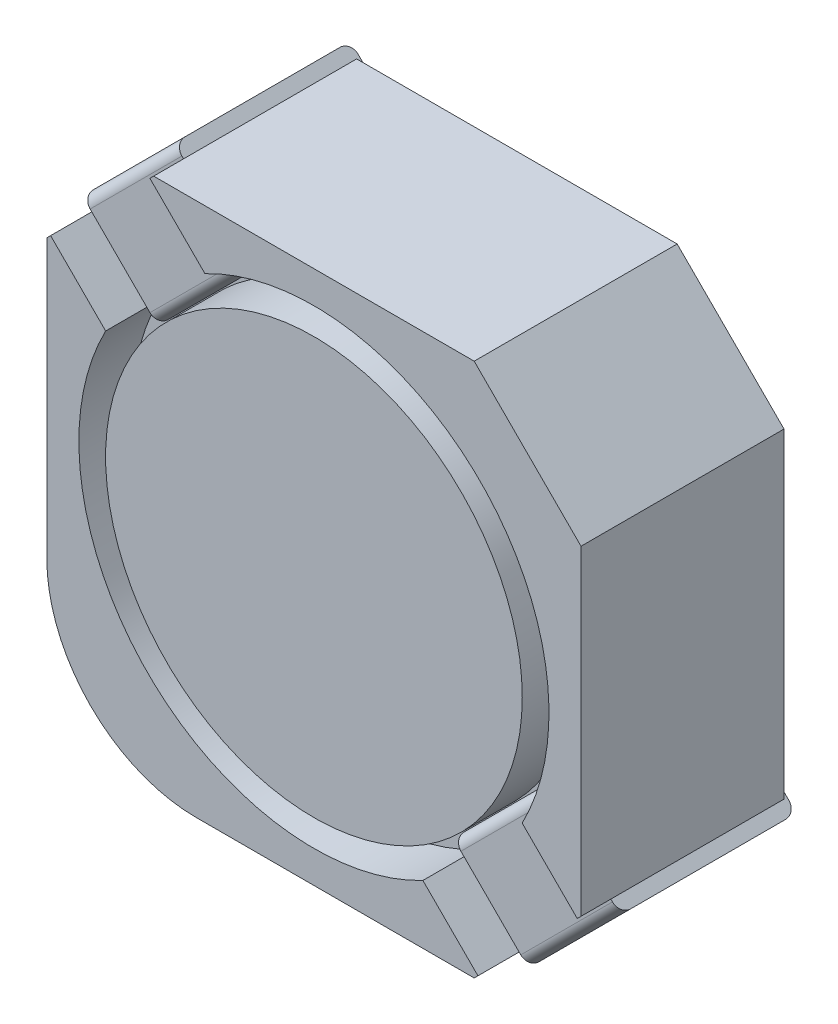
SolidWorks part; units mm, degrees
ref_plane "Спереди" through (0, 0, 0) normal (0, 0, 1) x (1, 0, 0)
ref_plane "Сверху" through (0, 0, 0) normal (0, 1, 0) x (1, 0, 0)
ref_plane "Справа" through (0, 0, 0) normal (1, 0, 0) x (0, 0, -1)
sketch "Эскиз2" plane through (0, 0, 0) normal (0, 0, 1) x (1, 0, 0)
  line L1 (-1.5, 2.5) -> (1.5, 2.5)
  line L2 (-2.5, 1.5) -> (-2.5, -1.1)
  line L3 (-1.1, -2.5) -> (1.5, -2.5)
  line L4 (2.5, 1.5) -> (2.5, -1.5)
  line L6 (-2.5, 1.5) -> (-1.5, 2.5)
  line L8 (1.5, 2.5) -> (2.5, 1.5)
  line L9 (1.5, -2.5) -> (2.5, -1.5)
  arc A0 (-2.5, -1.1) -> (-1.1, -2.5) centre (-1.1, -1.1) ccw
  point P0 (-2.5, 2.5)
  point P1 (2.5, -2.5)
  point P3 (2.5, 2.5)
  dimension "D1" = 1.4
extrude "Вытянуть1" add sketch "Эскиз2" along normal blind 1.9 from offset 0.1
sketch "Эскиз6" plane through (0, 0, 0) normal (0, 0, 1) x (1, 0, 0)
  circle A1 centre (0, 0) radius 2.2
extrude "Вытянуть5" cut sketch "Эскиз6" along normal blind 0.3
sketch "Эскиз8" plane through (0, 0, 0) normal (0, 0, 1) x (1, 0, 0)
  circle A0 centre (0, 0) radius 1.95
extrude "Вытянуть9" add sketch "Эскиз8" along normal blind 0.25 from offset 0.1
ref_plane "Плоскость1" through (-0.5, -0.5, 0) normal (0.7071, 0.7071, 0) x (0, 0, -1)
sketch "Эскиз10" plane through (-0.5, -0.5, 0) normal (0.7071, 0.7071, 0) x (0, 0, -1)
  line L0 (0, 2.0582) -> (0, 2.85)
  line L1 (-0.1, 2.95) -> (-1.55, 2.95)
  line L2 (-1.65, 2.85) -> (-1.65, 2.0582)
  line L3 (0, 0) -> (-3.3921, 0) construction
  line L4 (-1.55, -1.9582) -> (-0.1, -1.9582)
  line L5 (-1.55, 1.9582) -> (-0.1, 1.9582)
  line L6 (-1.65, -2.85) -> (-1.65, -2.0582)
  line L7 (-0.1, -2.95) -> (-1.55, -2.95)
  line L8 (0, -2.0582) -> (0, -2.85)
  arc A0 (0, 2.85) -> (-0.1, 2.95) centre (-0.1, 2.85) ccw
  arc A1 (0, 2.0582) -> (-0.1, 1.9582) centre (-0.1, 2.0582) cw
  arc A2 (-1.65, 2.0582) -> (-1.55, 1.9582) centre (-1.55, 2.0582) ccw
  arc A3 (-1.55, 2.95) -> (-1.65, 2.85) centre (-1.55, 2.85) ccw
  arc A4 (-1.55, -2.95) -> (-1.65, -2.85) centre (-1.55, -2.85) cw
  arc A5 (-1.65, -2.0582) -> (-1.55, -1.9582) centre (-1.55, -2.0582) cw
  arc A6 (0, -2.0582) -> (-0.1, -1.9582) centre (-0.1, -2.0582) ccw
  arc A7 (0, -2.85) -> (-0.1, -2.95) centre (-0.1, -2.85) cw
ref_plane "Плоскость2" through (0.5, 0.5, 0) normal (-0.7071, -0.7071, 0) x (0.7071, -0.7071, 0)
extrude "Вытянуть12" cut sketch "Эскиз6<3>" against normal blind 0.6 from offset 2.1
sketch "Эскиз6<3>" plane through (0, 0, 0) normal (0, 0, 1) x (1, 0, 0) same geometry as "Эскиз6"
sketch "Эскиз12" plane through (-0.5, -0.5, 0) normal (0.7071, 0.7071, 0) x (0, 0, -1)
  line L0 (-3.9996, 0) -> (-2.5383, 0) construction
  line L1 (-2.05, 2.8992) -> (-1.4, 2.8992)
  line L2 (-2.05, 2.8992) -> (-2.05, 2)
  line L3 (-2.05, 2) -> (-1.4, 2)
  line L4 (-1.4, 2.8992) -> (-1.4, 2)
  line L5 (0, 0) -> (-3.3921, 0) construction
  line L6 (-1.4, -2.8992) -> (-1.4, -2)
  line L7 (-2.05, -2) -> (-1.4, -2)
  line L8 (-2.05, -2.8992) -> (-2.05, -2)
  line L9 (-2.05, -2.8992) -> (-1.4, -2.8992)
extrude "Вытянуть15" cut sketch "Эскиз12" along normal offset from surface (1.3142 mm away) 0.05 from offset 0.05 up to plane "Плоскость2"
extrude "Вытянуть16" add sketch "Эскиз8<3>" against normal blind 0.7 from offset 2
sketch "Эскиз8<3>" plane through (0, 0, 0) normal (0, 0, 1) x (1, 0, 0) same geometry as "Эскиз8"
extrude "Вытянуть17" add sketch "Эскиз10" along normal offset from surface (1.2142 mm away) 0.1 from offset 0.1 up to plane "Плоскость2"
